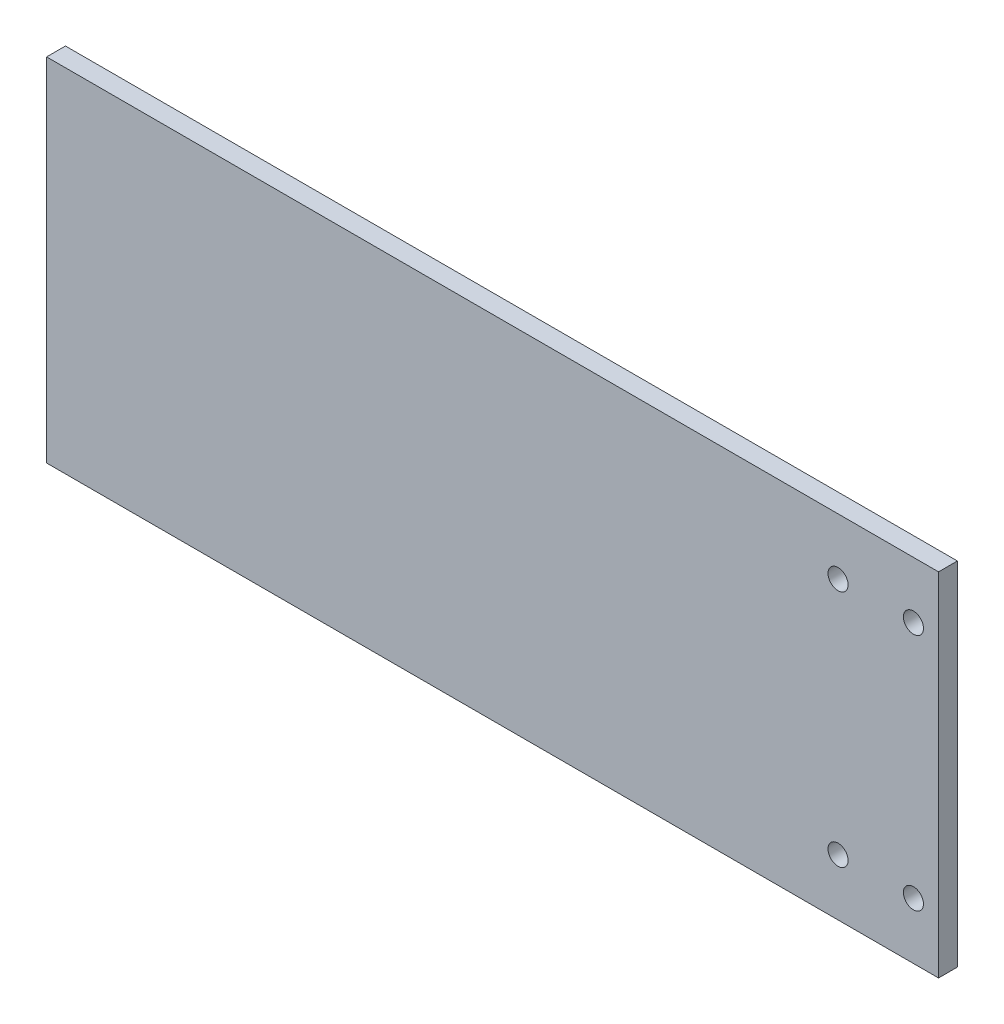
SolidWorks part; units mm, degrees
material "PEI"
ref_plane "Front Plane" through (0, 0, 0) normal (0, 0, 1) x (1, 0, 0)
ref_plane "Top Plane" through (0, 0, 0) normal (0, 1, 0) x (1, 0, 0)
ref_plane "Right Plane" through (0, 0, 0) normal (1, 0, 0) x (0, 0, -1)
sketch "Sketch2" plane through (0, 0, 0) normal (0, 0, 1) x (1, 0, 0)
  line L1 (56, -28) -> (-56, -28)
  line L2 (56, -28) -> (56, 28)
  line L3 (56, 28) -> (-56, 28)
  line L4 (-56, -28) -> (-56, 28)
  line L5 (56, -28) -> (-56, 28) construction
  line L6 (56, 28) -> (-56, -28) construction
  line L7 (56, 28) -> (86, 28)
  line L8 (56, 28) -> (56, -28)
  line L9 (56, -28) -> (86, -28)
  line L10 (86, 28) -> (86, -28)
  point P0 (0, 0)
  dimension "D1" = 112
  dimension "D2" = 56
  dimension "D3" = 30
extrude "Boss-Extrude1" add sketch "Sketch2" along normal blind 3 contours L4 L1 L2 L3 | L10 L7 L2 L9 region at (0, 0, 0) region at (71, 0, 0)
sketch "Sketch3" plane through (0, 0, 3) normal (0, 0, 1) x (1, 0, 0)
  line L0 (86, 28) -> (86, -28)
  line L1 (86, 28) -> (66, 28)
  line L2 (86, -28) -> (66, -28)
  line L3 (66, 28) -> (66, -28)
  line L4 (-56, 28) -> (-56, -28)
  line L5 (-56, -28) -> (86, -28)
  line L6 (86, -28) -> (86, 28)
  line L7 (86, 28) -> (-56, 28)
  line L8 (-56, 28) -> (-56, -28)
  line L9 (-56, -28) -> (86, -28)
  line L10 (86, -28) -> (86, 28)
  line L11 (86, 28) -> (-56, 28)
  line L12 (86, 28) -> (66, 28)
  line L13 (86, 19) -> (66, 19)
  line L14 (66, -19) -> (86, -19)
  line L15 (70, 28) -> (70, -24)
  line L16 (86, -24) -> (70, -24)
  line L17 (82, 28) -> (82, -28)
  circle A0 centre (70, 19) radius 1.6
  circle A1 centre (82, 19) radius 1.6
  circle A2 centre (82, -19) radius 1.6
  circle A3 centre (70, -19) radius 1.6
  point P23 (0, 0)
  point P25 (82, 19)
  point P27 (70, -19)
  dimension "D7" = 3.2
  dimension "D8" = 3.2
  dimension "D9" = 3.2
  dimension "D10" = 3.2
  dimension "D2" = 20
  dimension "D3" = 9
  dimension "D4" = 9
  dimension "D1" = 0
  dimension "D5" = 4
  dimension "D6" = 4
extrude "Cut-Extrude1" cut sketch "Sketch3" against normal through all contours L15 A3 L14 | L14 A3 L15 | L15 A3 L14 | L14 A3 L15 | L14 A2 L17 | L17 A2 L14 | L14 A2 L17 | L17 A2 L14 | L13 A1 L17 | L17 A1 L13 | L13 A1 L17 | L17 A1 L13 | L13 A0 L15 | L15 A0 L13 | L13 A0 L15 | L15 A0 L13 region at (82.6791, 18.3209, 3) region at (82.6791, 19.6791, 3) region at (81.3209, 19.6791, 3) region at (82.6791, -19.6791, 3) region at (82.6791, -18.3209, 3) region at (81.3209, 18.3209, 3) region at (70.6791, 19.6791, 3) region at (69.3209, 19.6791, 3) region at (81.3209, -19.6791, 3) region at (81.3209, -18.3209, 3) region at (69.3209, 18.3209, 3) region at (70.6791, 18.3209, 3) region at (69.3209, -19.6791, 3) region at (70.6791, -19.6791, 3) region at (70.6791, -18.3209, 3) region at (69.3209, -18.3209, 3)
